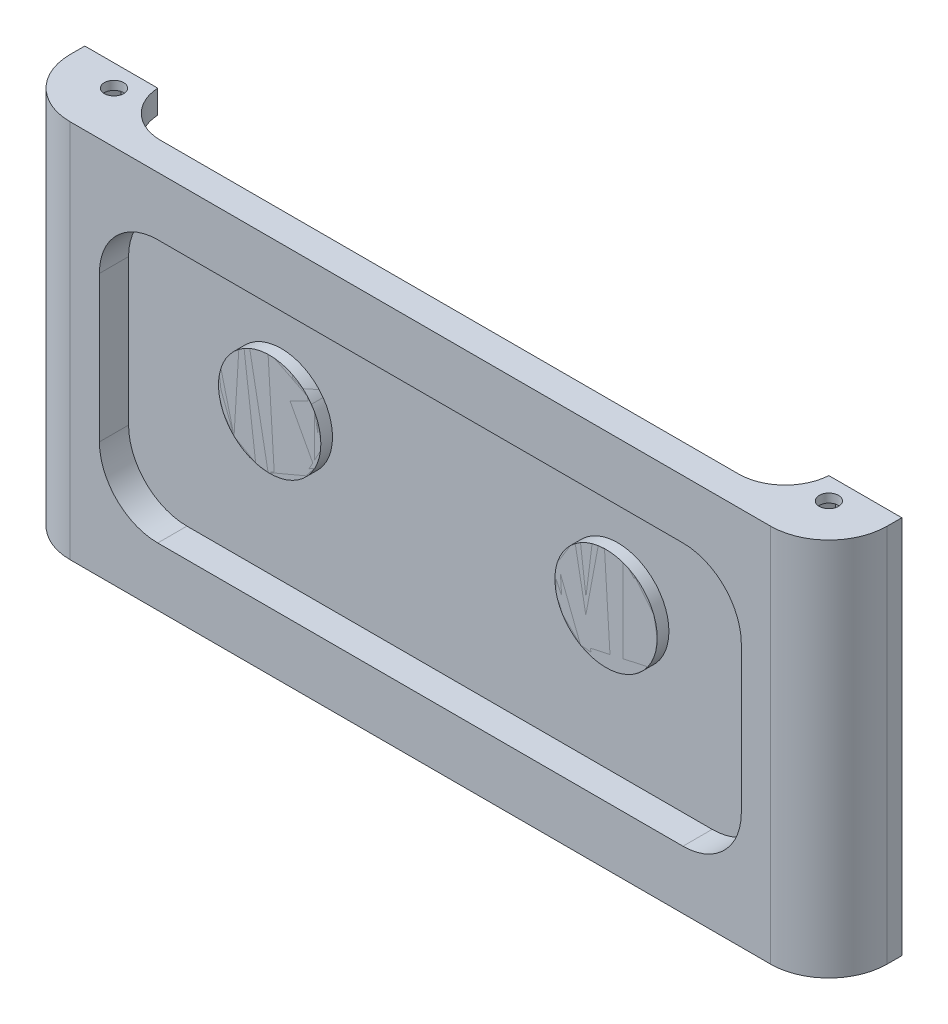
SolidWorks part; units mm, degrees
ref_plane "Front Plane" through (0, 0, 0) normal (0, 0, 1) x (1, 0, 0)
ref_plane "Top Plane" through (0, 0, 0) normal (0, 1, 0) x (1, 0, 0)
ref_plane "Right Plane" through (0, 0, 0) normal (1, 0, 0) x (0, 0, -1)
sketch "Sketch1" plane through (0, 0, 0) normal (0, 0, 1) x (1, 0, 0)
  line L1 (0, 0) -> (140, 0)
  line L2 (0, 0) -> (0, 65)
  line L3 (0, 65) -> (140, 65)
  line L4 (140, 0) -> (140, 65)
  point P6 (65.6215, 39.2286)
  point P12 (70, 45)
  dimension "D1" = 140
  dimension "D2" = 65
extrude "Boss-Extrude1" add sketch "Sketch1" along normal blind 12.5
sketch "Sketch4" plane through (0, 65, 0) normal (0, 1, 0) x (1, 0, 0)
  line L6 (5, 0) -> (135, 0)
  line L9 (135, 0) -> (135, -7.5)
  line L10 (5, -7.5) -> (5, 0)
  line L11 (135, -7.5) -> (5, -7.5)
  line L12 (135, 0) -> (135, -7.5)
  line L13 (5, -7.5) -> (5, 0)
  line L14 (135, -7.5) -> (5, -7.5)
  dimension "D1" = 5
extrude "Cut-Extrude3" cut sketch "Sketch4" against normal through all
sketch "Sketch2" plane through (0, 0, 12.5) normal (0, 0, 1) x (1, 0, 0)
  line L0 (70, 65) -> (70, 0) construction
  line L1 (140, 65) -> (0, 65) construction
  line L2 (0, 0) -> (140, 0) construction
  line L3 (140, 0) -> (140, 65) construction
  line L4 (15, 55) -> (125, 55)
  line L5 (15, 55) -> (15, 10)
  line L6 (15, 10) -> (125, 10)
  line L7 (125, 55) -> (125, 10)
  line L8 (15, 55) -> (125, 10) construction
  line L9 (15, 10) -> (125, 55) construction
  point P6 (70, 32.5)
  dimension "D1" = 15
  dimension "D2" = 10
extrude "Cut-Extrude1" cut sketch "Sketch2" against normal through all
fillet "Fillet1" radius 10 4 edges at (15, 10, 10) (15, 55, 10) (125, 10, 10) (125, 55, 10)
fillet "Fillet2" radius 10 2 edges at (140, 32.5, 12.5) (0, 32.5, 12.5)
sketch "Sketch5" plane through (0, 0, 0) normal (0, -1, 0) x (1, 0, 0)
  line L0 (0, 0) -> (5, 0) construction
  line L1 (5, 7.5) -> (12.5, 7.5)
  line L2 (5, 7.5) -> (5, 0)
  line L3 (5, 0) -> (12.5, 0)
  line L4 (12.5, 7.5) -> (12.5, 0)
  line L5 (135, 7.5) -> (127.5, 7.5)
  line L6 (135, 7.5) -> (135, 0)
  line L7 (135, 0) -> (127.5, 0)
  line L8 (127.5, 7.5) -> (127.5, 0)
extrude "Boss-Extrude2" add sketch "Sketch5" against normal blind 4
sketch "Sketch6" plane through (0, 4, 0) normal (0, 1, 0) x (1, 0, 0)
  line L0 (8.75, 0) -> (8.75, -7.5) construction
  line L1 (11.9254, -3.75) -> (10.3377, -1)
  line L2 (10.3377, -1) -> (7.1623, -1)
  line L3 (7.1623, -1) -> (5.5746, -3.75)
  line L4 (5.5746, -3.75) -> (7.1623, -6.5)
  line L5 (7.1623, -6.5) -> (10.3377, -6.5)
  line L6 (10.3377, -6.5) -> (11.9254, -3.75)
  line L7 (5, 0) -> (12.5, 0) construction
  line L8 (12.5, -7.5) -> (5, -7.5) construction
  line L9 (70, -12.5) -> (70, 1.5241) construction
  line L10 (130, -12.5) -> (10, -12.5) construction
  line L11 (134.4254, -3.75) -> (132.8377, -6.5)
  line L12 (132.8377, -6.5) -> (129.6623, -6.5)
  line L13 (129.6623, -6.5) -> (128.0746, -3.75)
  line L14 (128.0746, -3.75) -> (129.6623, -1)
  line L15 (129.6623, -1) -> (132.8377, -1)
  line L16 (132.8377, -1) -> (134.4254, -3.75)
  circle A0 centre (8.75, -3.75) radius 2.75 construction
  circle A1 centre (8.75, -3.75) radius 1.65
  circle A2 centre (131.25, -3.75) radius 1.65
  point P21 (10.0949, -1.4206)
  dimension "D1" = 3.3
  dimension "D2" = 5.5
extrude "Cut-Extrude5" cut sketch "Sketch6<2>" against normal through all contours A1 | A2 region at (8.75, 4, 3.75) region at (131.25, 4, 3.75)
sketch "Sketch6<2>" plane through (0, 4, 0) normal (0, 1, 0) x (1, 0, 0) same geometry as "Sketch6"
extrude "Cut-Extrude4" cut sketch "Sketch6" against normal blind 2.5
fillet "Fillet3" radius 8 2 edges at (127.5, 2, 7.5) (12.5, 2, 7.5)
ref_plane "Plane1" through (0, 32.5, 0) normal (0, 1, 0) x (1, 0, 0)
mirror "Mirror1" about plane through (0, 32.5, 0) normal (0, 1, 0) of "Cut-Extrude5", "Cut-Extrude4", "Boss-Extrude2", "Fillet3"
sketch "Sketch7" plane through (0, 0, 7.5) normal (0, 0, -1) x (-1, 0, 0)
  line L1 (-135, 61) -> (-5, 61)
  line L2 (-135, 61) -> (-135, 4)
  line L3 (-135, 4) -> (-5, 4)
  line L4 (-5, 61) -> (-5, 4)
extrude "Boss-Extrude3" add sketch "Sketch7" along normal blind 1 separate body
sketch "Sketch8" plane through (0, 0, 7.5) normal (0, 0, 1) x (1, 0, 0)
  line L0 (70, 55) -> (70, 24.7719) construction
  line L1 (115, 55) -> (25, 55) construction
  line L2 (25, 10) -> (115, 10) construction
  line L3 (41.1771, 35.6804) -> (98.8229, 35.6804) construction
  line L5 (70, 19.7719) -> (70, 10) construction
  circle A0 centre (41.1771, 35.6804) radius 8.769
  circle A1 centre (98.8229, 35.6804) radius 8.769
  point P11 (70, 35.6804)
  point P12 (98.8229, 49.731)
extrude "Boss-Extrude4" add sketch "Sketch8" along normal blind 2 separate body contours A0 | A1 region at (41.1771, 35.6804, 7.5) region at (98.8229, 35.6804, 7.5)
extrude "Boss-Extrude5" add sketch "Sketch8<3>" along normal blind 2 separate body
sketch "Sketch8<3>" plane through (0, 0, 7.5) normal (0, 0, 1) x (1, 0, 0) same geometry as "Sketch8"
